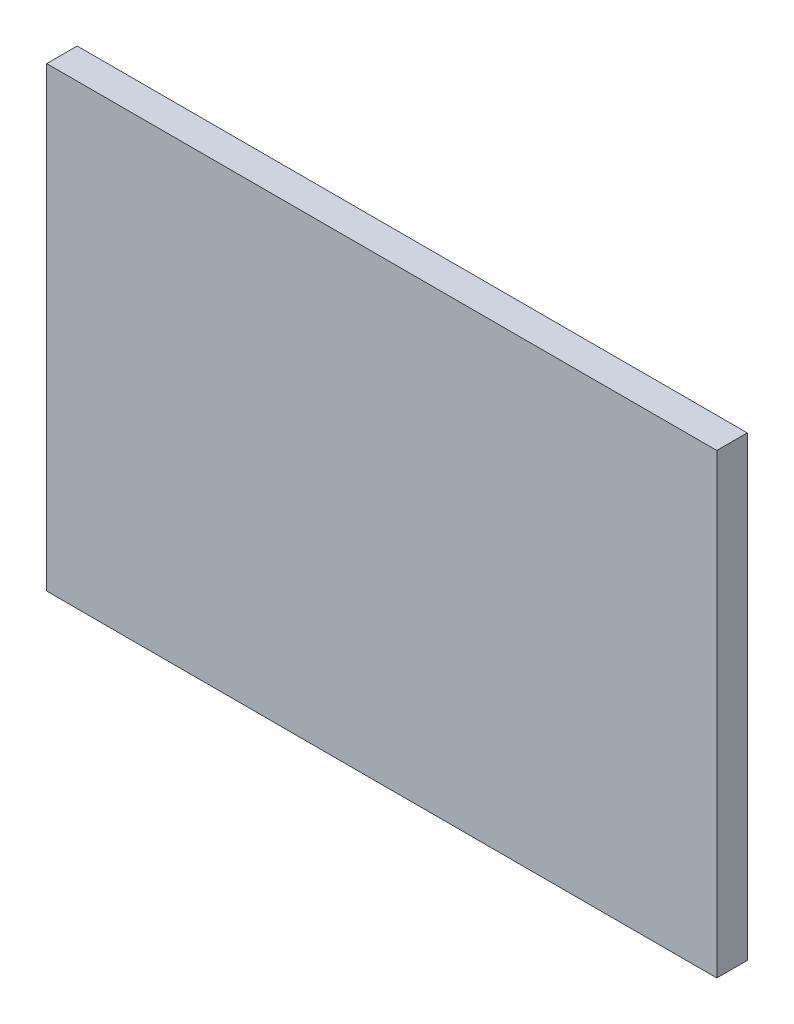
SolidWorks part; units mm, degrees
material "Nickel"
ref_plane "Plane1" through (0, 0, 0) normal (0, 0, 1) x (1, 0, 0)
ref_plane "Plane2" through (0, 0, 0) normal (0, 1, 0) x (1, 0, 0)
ref_plane "Plane3" through (0, 0, 0) normal (1, 0, 0) x (0, 0, -1)
sketch "Sketch1" plane through (0, 0, 0) normal (0, 0, 1) x (1, 0, 0)
  line L0 (-11, -0.0588) -> (11, -0.0588)
  line L1 (0, -10) -> (0, 14.9412) construction
  line L3 (11, 14.9412) -> (11, -0.0588)
  line L4 (11, 14.9412) -> (-11, 14.9412)
  line L5 (-11, 14.9412) -> (-11, -0.0588)
  dimension "D3" = 11
  dimension "D4" = 15
extrude "Extrude1" add sketch "Sketch1" along normal blind 1
sketch "Sketch2" plane through (11, 0, 0) normal (1, 0, 0) x (0, 0, -1)
  line L0 (-1, 14.9412) -> (-7.6228, 14.9412) construction
  circle A0 centre (-4.5, 14.9412) radius 4.5
  circle A1 centre (-4.5, 14.9412) radius 3.5
  dimension "D1" = 7
ref_axis "Axis3" through (-10.8102, 14.9412, 4.5) along (1, 0, 0)
sketch "Sketch5" plane through (-11, 0, 0) normal (-1, 0, 0) x (0, 0, 1)
  point P0 (4.5, 14.9412)
sketch "FilterSketch" plane through (11, 0, 0) normal (1, 0, 0) x (0, 0, -1)
  circle A0 centre (-4.5, 14.9412) radius 3 construction
  circle A1 centre (-4.5, 14.9412) radius 0.05 construction
  circle A2 centre (-4.5, 14.9412) radius 3.25 construction
  dimension "NominalDiameter" = 6
  dimension "InnerDiameter" = 0.1
  dimension "OuterDiameter" = 6.5
other "RPoint1"
ref_axis "Axis4" through (16, 14.9412, 4.5) along (-1, 0, 0)
other "RPoint2"
ref_axis "Axis5" through (-16, 14.9412, 4.5) along (1, 0, 0)
